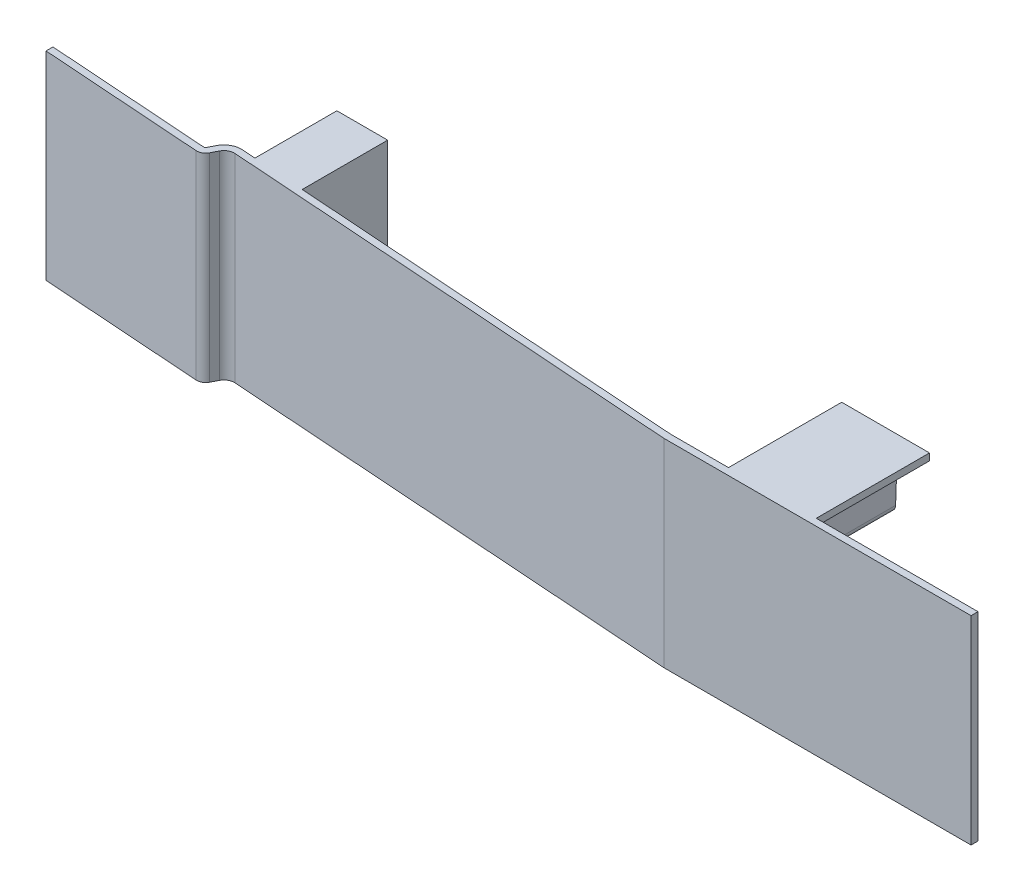
SolidWorks part; units mm, degrees
ref_plane "Plan de face" through (0, 0, 0) normal (0, 0, 1) x (1, 0, 0)
ref_plane "Plan de dessus" through (0, 0, 0) normal (0, 1, 0) x (1, 0, 0)
ref_plane "Plan de droite" through (0, 0, 0) normal (1, 0, 0) x (0, 0, -1)
sketch "Esquisse1" plane through (0, 0, 0) normal (0, 1, 0) x (1, 0, 0)
  line L0 (43, 0) -> (-90, 0)
  line L1 (-90, 0) -> (-289.5128, 13.9513)
  line L2 (-283.5, 16.5382) -> (-289.3035, 16.944)
  line L3 (-289.5128, 13.9513) -> (-298.4909, 14.5791) construction
  line L4 (-292.5055, 14.1606) -> (-296.4511, 6.4169) construction
  line L5 (43, 3) -> (-89.8952, 3)
  line L6 (-89.8952, 3) -> (-261.5, 14.9998)
  line L7 (-368.8784, 11.4815) -> (-290.0709, 5.9708) construction
  line L8 (-289.3035, 16.944) -> (-289.5128, 13.9513) construction
  line L9 (-89.8952, 3) -> (-290.0448, 16.9958) construction
  line L10 (43, 0) -> (43, 3)
  line L11 (-283.5, 16.5382) -> (-283.5, 52)
  line L12 (-283.5, 52) -> (-261.5, 52)
  line L13 (-261.5, 52) -> (-261.5, 14.9998)
  line L14 (-258.0213, 12.2989) -> (-258.0213, 12.2989) construction
  line L15 (-239.4174, 16.3409) -> (-258.0656, 15.2985) construction
  line L16 (-289.5128, 13.9513) -> (-290.0709, 5.9708) construction
  line L17 (-436.8227, 2.3283) -> (-258.0213, 12.2989) construction
  line L18 (-290.0448, 16.9958) -> (-436.8227, 2.3283) construction
  line L19 (-290, 13.9854) -> (-300.5302, 12.9331) construction
  line L20 (-300.5302, 12.9331) -> (-239.4174, 16.3409) construction
  line L21 (-90, 0) -> (-290, 13.9854) construction
  line L22 (-289.829, 9.4298) -> (-293.8675, 11.4875) construction
  line L23 (-293.8675, 11.4875) -> (-296.5405, 12.8495) construction
  line L24 (-298.4909, 14.5791) -> (-299.0489, 6.5986) construction
  line L25 (-368.8784, 11.4815) -> (-299.0489, 6.5986)
  line L26 (-293.8675, 11.4875) -> (-295.2688, 8.7373)
  line L27 (-298.7745, 10.5235) -> (-295.2688, 8.7373) construction
  line L28 (-296.5405, 12.8495) -> (-297.9418, 10.0993)
  line L29 (-368.8784, 11.4815) -> (-368.8784, 14.4889)
  line L32 (-298.8397, 9.5913) -> (-368.8784, 14.4889)
  arc A0 (-289.5128, 13.9513) -> (-293.8675, 11.4875) centre (-289.829, 9.4298) ccw
  arc A1 (-289.3035, 16.944) -> (-296.5405, 12.8495) centre (-289.829, 9.4298) ccw
  arc A2 (-299.0489, 6.5986) -> (-295.2688, 8.7373) centre (-298.7745, 10.5235) ccw
  arc A3 (-297.9418, 10.0993) -> (-298.8397, 9.5913) centre (-298.7745, 10.5235) cw
  dimension "D10" = 90
  dimension "D11" = 9
  dimension "D2" = 90
  dimension "D3" = 43
  dimension "D4" = 4
  dimension "D5" = 200
  dimension "D6" = 67
  dimension "D7" = 203
  dimension "D8" = 8
  dimension "D9" = 90
  dimension "D12" = 22
  dimension "D13" = 261.5
  dimension "D14" = 49
  dimension "D15" = 90
  dimension "D16" = 70
  dimension "D19" = 3
  dimension "D1" = 3
extrude "Extrusion1" add sketch "Esquisse1" along normal blind 43 and the other way blind 43
sketch "Esquisse2" plane through (0, 0, -3) normal (0, 0, -1) x (-1, 0, 0)
  line L0 (27, 43) -> (27, 40)
  line L1 (-43, 43) -> (89.8952, 43) construction
  line L2 (27, 40) -> (36, 40)
  line L3 (40.997, 35.1745) -> (41.6665, 16)
  line L4 (44.6665, 13) -> (56.3684, 13)
  line L5 (59.3684, 16) -> (60.003, 34.1745)
  line L7 (65, 39) -> (65, 43)
  line L8 (65, 43) -> (27, 43)
  arc A0 (60.003, 34.1745) -> (65, 39) centre (65, 34) cw
  arc A1 (59.3684, 16) -> (56.3684, 13) centre (56.2598, 16.1086) cw
  arc A2 (44.6665, 13) -> (41.6665, 16) centre (44.6665, 16) cw
  arc A3 (36, 40) -> (40.997, 35.1745) centre (36, 35) cw
  dimension "D5" = 5
  dimension "D10" = 3
  dimension "D1" = 27
  dimension "D2" = 38
  dimension "D3" = 30
  dimension "D4" = 4
  dimension "D6" = 92
  dimension "D7" = 92
  dimension "D8" = 0
  dimension "D9" = 9
  dimension "D11" = 3
  dimension "D12" = 3
  dimension "D13" = 3
extrude "Extrusion2" add sketch "Esquisse2" along normal up to surface (49 mm away) up to face at (-272.5, 0, -52)
